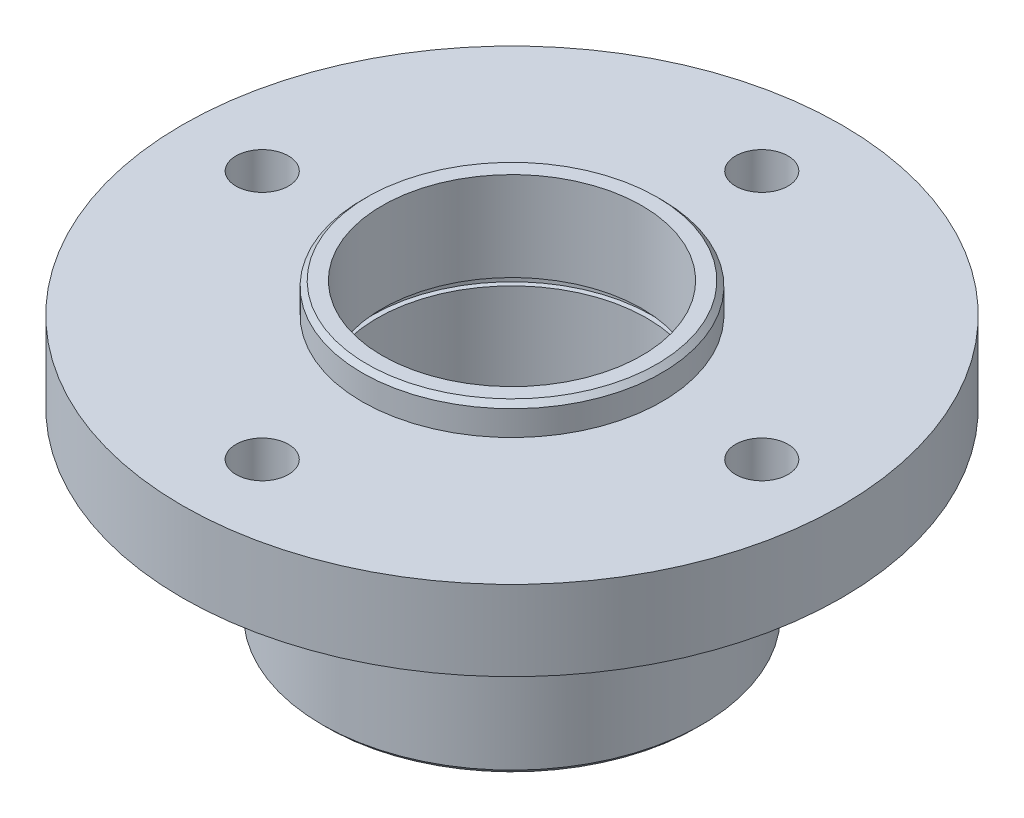
SolidWorks part; units mm, degrees
material "7050-T7451"
ref_plane "Płaszczyzna przednia" through (0, 0, 0) normal (0, 0, 1) x (1, 0, 0)
ref_plane "Płaszczyzna górna" through (0, 0, 0) normal (0, 1, 0) x (1, 0, 0)
ref_plane "Płaszczyzna prawa" through (0, 0, 0) normal (1, 0, 0) x (0, 0, -1)
sketch "Szkic1" plane through (0, 0, 0) normal (0, 0, 1) x (1, 0, 0)
  line L0 (0, 0) -> (0, 84.3909) construction
  line L1 (30, 80.9231) -> (66, 80.9231)
  line L2 (66, 80.9231) -> (66, 64.9231)
  line L3 (66, 64.9231) -> (38, 64.9231)
  line L4 (38, 64.9231) -> (38, 39.9231)
  line L8 (38, 39.9231) -> (38, 28.9231)
  line L9 (37, 27.9231) -> (24.5, 27.9231)
  line L10 (24.5, 27.9231) -> (24.5, 29.9231)
  line L11 (24.5, 29.9231) -> (27, 29.9231)
  line L12 (27, 29.9231) -> (27, 66.9231)
  line L13 (27, 66.9231) -> (28, 66.9231)
  line L14 (28, 66.9231) -> (28, 69.0731)
  line L15 (28, 69.0731) -> (26, 69.0731)
  line L16 (26, 69.0731) -> (26, 80.9231)
  line L17 (26, 80.9231) -> (26, 86.9231)
  line L18 (26, 86.9231) -> (29, 86.9231)
  line L19 (30, 85.9231) -> (30, 80.9231)
  line L20 (29, 86.9231) -> (30, 85.9231)
  line L21 (38, 28.9231) -> (37, 27.9231)
  point P5 (38, 27.9231)
  point P19 (30, 86.9231)
  dimension "D1" = 40
  dimension "D2" = 26
  dimension "D3" = 16
  dimension "D4" = 28
  dimension "D5" = 25
  dimension "D10" = 13.5
  dimension "D11" = 2
  dimension "D12" = 2.5
  dimension "D13" = 37
  dimension "D14" = 1
  dimension "D15" = 2.15
  dimension "D16" = 4
  dimension "D17" = 6
revolve "Obrót1" add sketch "Szkic1" angle 360 about L0
sketch "Szkic2" plane through (0, 80.9231, 0) normal (0, 1, 0) x (1, 0, 0)
  point P0 (-50, 0)
  point P5 (0, 50)
  point P6 (50, 0)
  point P7 (0, -50)
  dimension "D1" = 50
  dimension "D2" = 4
hole_wizard "Otwór gwintowany M12x1.51" positions "Szkic 3D2" profile "Szkic4" tap size "M12x1.5" standard "DIN" end condition up to next
sketch3d "Szkic 3D2"
  point P0 (-50, 80.9231, 0)
  point P3 (0, 80.9231, -50)
  point P6 (50, 80.9231, 0)
  point P9 (0, 80.9231, 50)
sketch "Szkic4" plane through (-50, 80.9231, 0) normal (1, 0, 0) x (0, 0, 1)
  line L0 (0, 0) -> (0, 16)
  line L1 (0, 16) -> (5.25, 16)
  line L2 (5.25, 16) -> (5.25, 0)
  line L5 (5.25, 0) -> (0, 0)
  line L11 (0, -6.35) -> (0, 107.95) construction
  dimension "Średnica otworu gwintowanego na wylot" = 10.5
  dimension "Głębokość otworu gwintowanego na wylot" = 16
cosmetic thread "Gwint otworu1" parameters "D2"=12
cosmetic thread "Gwint otworu2" parameters "D2"=12
cosmetic thread "Gwint otworu3" parameters "D2"=12
cosmetic thread "Gwint otworu4" parameters "D2"=12
